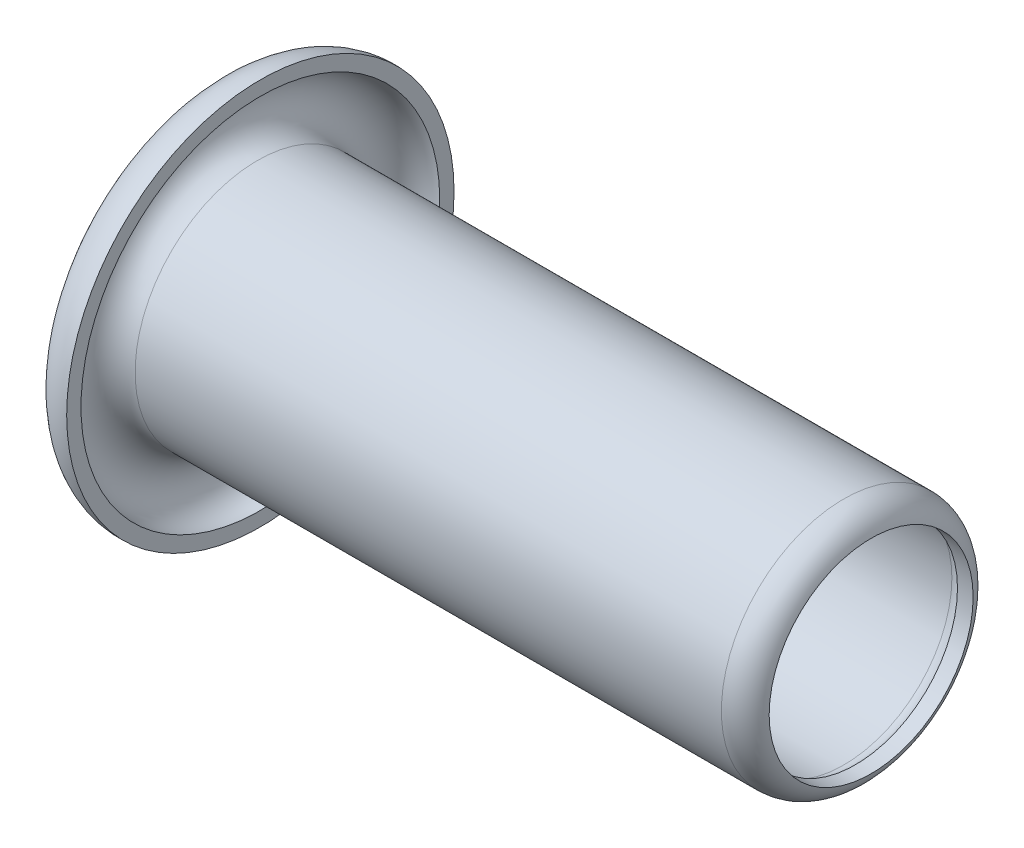
SolidWorks part; units mm, degrees
ref_plane "Front" through (0, 0, 0) normal (0, 0, 1) x (1, 0, 0)
ref_plane "Top" through (0, 0, 0) normal (0, 1, 0) x (1, 0, 0)
ref_plane "Right" through (0, 0, 0) normal (1, 0, 0) x (0, 0, -1)
sketch "Sketch1" plane through (2.0982, 0.9018, 0) normal (0, 0, 1) x (0, 1, 0)
  line L0 (3.4947, 0.9782) -> (3.8459, 0.9782)
  line L1 (2.0982, 1.0482) -> (2.0982, -13.3218)
  line L2 (1.3982, -14.0218) -> (-0.9018, -14.0218)
  line L3 (1.7482, -13.3218) -> (1.7482, 1.0482)
  line L4 (-0.9018, -14.0218) -> (-0.9018, 3) construction
  line L5 (2.7982, 2.0982) -> (-0.9398, 2.0982) construction
  line L6 (1.3982, -13.6718) -> (-0.9018, -13.6718)
  line L7 (-0.9018, -13.6718) -> (-0.9018, -14.0218)
  arc A0 (3.4947, 0.9782) -> (2.0982, 1.0482) centre (2.7982, 1.0482) ccw
  arc A1 (3.8459, 0.9782) -> (1.7482, 1.0482) centre (2.7982, 1.0482) ccw
  arc A2 (1.3982, -13.6718) -> (1.7482, -13.3218) centre (1.3982, -13.3218) ccw
  arc A3 (2.0982, -13.3218) -> (1.3982, -14.0218) centre (1.3982, -13.3218) cw
  dimension "r" = 0.7
  dimension "l" = 15
  dimension "K" = 1.12
  dimension "D1" = 0.35
revolve "Base-Revolve" add sketch "Sketch1" angle 360 about L4
sketch "Sketch2" plane through (0, 0, 0) normal (0, 0, 1) x (1, 0, 0)
  line L0 (0, 0) -> (17.7089, 0) construction
  line L1 (16.12, -2.3) -> (16.12, 2.3) construction
  line L2 (16.62, 0) -> (14.92, 0)
  line L3 (16.62, 0) -> (16.62, 2.5)
  line L4 (16.62, 2.5) -> (14.92, 2.5)
  line L5 (14.92, 0) -> (14.92, 2.5)
  line L6 (15.42, 3) -> (15.42, -3) construction
  dimension "D1" = 0.5
  dimension "D2" = 0.5
  dimension "dt" = 5
revolve "Cut-Revolve1" cut sketch "Sketch2" angle 360 about L0
equation "\"D1@Sketch1\" = \"δ@Sketch1\""
equation "\"D2@Sketch1\" = \"D1@Sketch1\""
